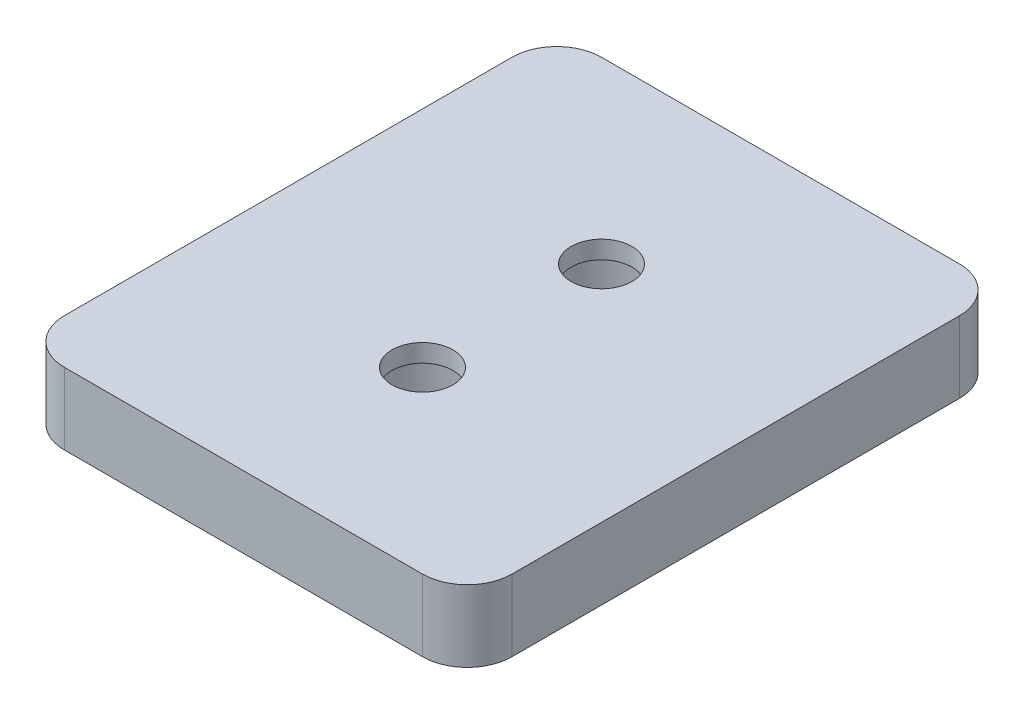
SolidWorks part; units mm, degrees
ref_plane "Front Plane" through (0, 0, 0) normal (0, 0, 1) x (1, 0, 0)
ref_plane "Top Plane" through (0, 0, 0) normal (0, 1, 0) x (1, 0, 0)
ref_plane "Right Plane" through (0, 0, 0) normal (1, 0, 0) x (0, 0, -1)
sketch "Sketch1" plane through (0, 0, 0) normal (0, 1, 0) x (1, 0, 0)
  line L1 (0, 0) -> (25, 0)
  line L2 (0, 0) -> (0, 30)
  line L3 (0, 30) -> (25, 30)
  line L4 (25, 0) -> (25, 30)
  dimension "D1" = 30
  dimension "D2" = 25
extrude "Boss-Extrude1" add sketch "Sketch1" along normal blind 4
hole_wizard "CBORE for M3 SHCS2" positions "Sketch3" profile "Sketch4" counterbore size "M3" standard "ANSI Metric" end condition through all
sketch "Sketch3" plane through (0, 0, 0) normal (0, -1, 0) x (-1, 0, 0)
  line L0 (0, 30) -> (0, 0) construction
  line L1 (0, 0) -> (-25, 0) construction
  line L2 (-12.5, 10) -> (-12.5, 20)
  line L3 (-12.5, 15) -> (0, 15)
  point P0 (-12.5, 20)
  point P8 (-12.5, 0)
  point P31 (-12.5, 10)
  dimension "D1" = 10
sketch "Sketch4" plane through (12.5, 0, -20) normal (1, 0, 0) x (0, 0, -1)
  line L0 (0, 0) -> (0, 4)
  line L1 (0, 4) -> (1.7, 4)
  line L3 (1.7, 4) -> (1.7, 3)
  line L4 (1.7, 3) -> (3.25, 3)
  line L5 (3.25, 3) -> (3.25, 0)
  line L7 (3.25, 0) -> (0, 0)
  line L11 (0, -6.35) -> (0, 107.95) construction
  dimension "Thru Hole Dia." = 3.4
  dimension "Thru Hole Depth" = 4
  dimension "C'Bore Dia." = 6.5
  dimension "C'Bore Depth" = 3
fillet "Fillet1" radius 2.5 4 edges at (0, 2, -30) (0, 2, 0) (25, 2, 0) (25, 2, -30)
